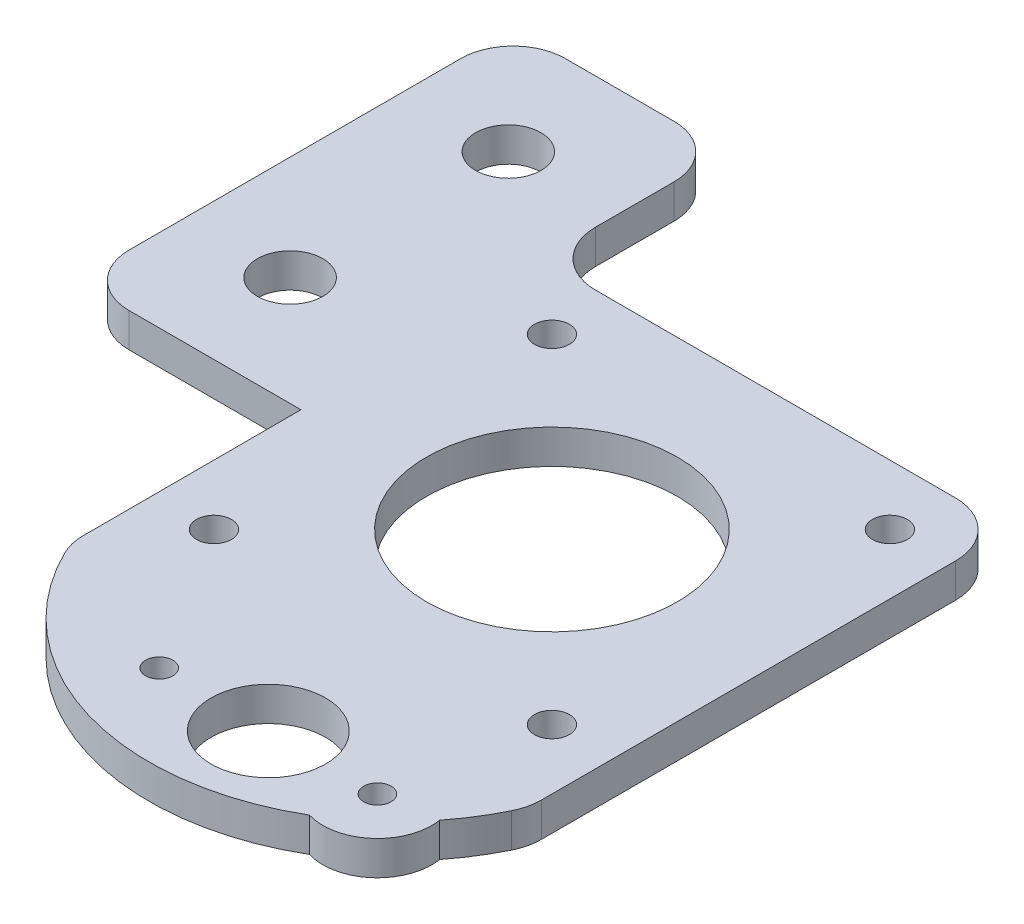
SolidWorks part; units mm, degrees
note: '?' marks a value the reader was unsure of.
ref_plane "Front Plane" through (0, 0, 0) normal (0, 0, 1) x (1, 0, 0)
ref_plane "Top Plane" through (0, 0, 0) normal (0, 1, 0) x (1, 0, 0)
ref_plane "Right Plane" through (0, 0, 0) normal (1, 0, 0) x (0, 0, -1)
ref_plane "Plane1" through (0, 546.875, 0) normal (0, -1, 0) x (1, 0, 0)
sketch "Sketch11" plane through (0, 546.875, 0) normal (0, -1, 0) x (1, 0, 0)
  line L0 (22.4103, -39.5068) -> (32.3733, -39.5068)
  line L1 (37.1733, -34.7068) -> (37.1733, -27.5068)
  line L2 (42.1733, -22.5068) -> (75.1733, -22.5068)
  line L3 (80.1733, -17.5068) -> (80.1733, 20.4615)
  line L4 (38.1828, 20.4638) -> (38.1662, 0.4932)
  line L5 (38.1662, 0.4932) -> (22.4103, 0.4932)
  line L6 (17.6103, -4.3068) -> (17.6103, -34.7068)
  arc A0 (17.6103, -34.7068) -> (22.4103, -39.5068) centre (22.4103, -34.7068) ccw
  arc A1 (32.3733, -39.5068) -> (37.1733, -34.7068) centre (32.3733, -34.7068) ccw
  arc A2 (37.1733, -27.5068) -> (42.1733, -22.5068) centre (42.1733, -27.5068) cw
  arc A3 (75.1733, -22.5068) -> (80.1733, -17.5068) centre (75.1733, -17.5068) ccw
  arc A4 (80.1733, 20.4615) -> (79.661, 22.666) centre (75.1733, 20.4615) ccw
  arc A5 (79.661, 22.666) -> (77.1125, 26.7162) centre (59.1785, 12.6046) ccw
  arc A6 (77.1125, 26.7162) -> (70.7355, 32.2821) centre (72.1733, 27.4932) ccw
  arc A7 (70.7355, 32.2821) -> (38.6947, 22.6637) centre (59.1785, 12.6046) ccw
  arc A8 (38.6947, 22.6637) -> (38.1828, 20.4638) centre (43.1828, 20.4597) ccw
  arc A9 (22.4103, 0.4932) -> (17.6103, -4.3068) centre (22.4103, -4.3068) ccw
base flange "Base-Flange1" sketch "Sketch11" thickness 3.125 reverse thickness direction yes parameters "D1"=0
hole_wizard "Ø10.5 (10.5) Diameter Hole1" positions "Sketch17" profile "Sketch16" hole size "Ø10.5" standard "ANSI Metric"
sketch "Sketch17" plane through (0, 546.875, 0) normal (0, -1, 0) x (-1, 0, 0)
  point P0 (-62.1733, -27.4932)
sketch "Sketch16" plane through (62.1733, 546.875, 27.4932) normal (1, 0, 0) x (0, 0, -1)
  line L0 (0, 0) -> (0, 3.125)
  line L1 (0, 3.125) -> (5.25, 3.125)
  line L2 (5.25, 3.125) -> (5.25, 0)
  line L5 (5.25, 0) -> (0, 0)
  line L11 (0, -6.35) -> (0, 107.95) construction
  dimension "Thru Hole Dia." = 10.5
  dimension "Thru Hole Depth" = 3.125
hole_wizard "Ø3.2 (3.2) Diameter Hole1" positions "Sketch19" profile "Sketch18" hole size "Ø3.2" standard "ANSI Metric"
sketch "Sketch19" plane through (0, 546.875, 0) normal (0, -1, 0) x (-1, 0, 0)
  point P0 (-74.6642, -13.9842)
  point P1 (-43.6823, -13.9842)
  point P2 (-43.6823, 16.9977)
  point P3 (-74.6642, 16.9977)
sketch "Sketch18" plane through (74.6642, 546.875, 13.9842) normal (1, 0, 0) x (0, 0, -1)
  line L0 (0, 0) -> (0, 3.125)
  line L1 (0, 3.125) -> (1.6, 3.125)
  line L2 (1.6, 3.125) -> (1.6, 0)
  line L5 (1.6, 0) -> (0, 0)
  line L11 (0, -6.35) -> (0, 107.95) construction
  dimension "Thru Hole Dia." = 3.2
  dimension "Thru Hole Depth" = 3.125
hole_wizard "Ø23.0 (23) Diameter Hole1" positions "Sketch21" profile "Sketch20" hole size "Ø23.0" standard "ANSI Metric"
sketch "Sketch21" plane through (0, 546.875, 0) normal (0, -1, 0) x (-1, 0, 0)
  point P0 (-59.1733, 1.5068)
sketch "Sketch20" plane through (59.1733, 546.875, -1.5068) normal (1, 0, 0) x (0, 0, -1)
  line L0 (0, 0) -> (0, 3.125)
  line L1 (0, 3.125) -> (11.5, 3.125)
  line L2 (11.5, 3.125) -> (11.5, 0)
  line L5 (11.5, 0) -> (0, 0)
  line L11 (0, -6.35) -> (0, 107.95) construction
  dimension "Thru Hole Dia." = 23
  dimension "Thru Hole Depth" = 3.125
hole_wizard "Ø6.0 (6) Diameter Hole1" positions "Sketch23" profile "Sketch22" hole size "Ø6.0" standard "ANSI Metric"
sketch "Sketch23" plane through (0, 546.875, 0) normal (0, -1, 0) x (-1, 0, 0)
  point P0 (-27.1733, 9.5068)
  point P1 (-27.1733, 29.5068)
sketch "Sketch22" plane through (27.1733, 546.875, -9.5068) normal (1, 0, 0) x (0, 0, -1)
  line L0 (0, 0) -> (0, 3.125)
  line L1 (0, 3.125) -> (3, 3.125)
  line L2 (3, 3.125) -> (3, 0)
  line L5 (3, 0) -> (0, 0)
  line L11 (0, -6.35) -> (0, 107.95) construction
  dimension "Thru Hole Dia." = 6
  dimension "Thru Hole Depth" = 3.125
hole_wizard "Ø2.5 (2.5) Diameter Hole1" positions "Sketch25" profile "Sketch24" hole size "Ø2.5" standard "ANSI Metric"
sketch "Sketch25" plane through (0, 546.875, 0) normal (0, -1, 0) x (-1, 0, 0)
  point P0 (-72.1733, -27.4932)
  point P1 (-52.1733, -27.4932)
sketch "Sketch24" plane through (72.1733, 546.875, 27.4932) normal (1, 0, 0) x (0, 0, -1)
  line L0 (0, 0) -> (0, 3.125)
  line L1 (0, 3.125) -> (1.25, 3.125)
  line L2 (1.25, 3.125) -> (1.25, 0)
  line L5 (1.25, 0) -> (0, 0)
  line L11 (0, -6.35) -> (0, 107.95) construction
  dimension "Thru Hole Dia." = 2.5
  dimension "Thru Hole Depth" = 3.125
ref_point "Point1"
ref_axis "Axis1" through (27.1733, 550, -29.5068) along (0, -1, 0)?
ref_axis "Axis2" through (27.1733, 550, -9.5068) along (0, -1, 0)?
ref_axis "Axis3" through (62.1733, 550, 27.4932) along (0, -1, 0)?
ref_axis "Axis4" through (59.1733, 550, -1.5068) along (0, -1, 0)?
sketch "Bend-Lines4" plane through (0, 0, 0) normal (0, 1, 0) x (1, 0, 0)
sketch "Bounding-Box4" plane through (0, 0, 0) normal (0, 1, 0) x (1, 0, 0)
sheet metal parameters "Sheet-Metal(6)" thickness 3.125 parameters "D1"=0
flat pattern "Flat-Pattern(6)" [suppressed]
sketch "Bend-Lines5" plane through (0, 0, 0) normal (0, 1, 0) x (1, 0, 0)
sketch "Bounding-Box5" [suppressed] plane through (0, 0, 0) normal (0, 1, 0) x (1, 0, 0)
sheet metal parameters "Sheet-Metal(7)" thickness 3.125 parameters "D1"=0
flat pattern "Flat-Pattern(6)"
sketch "Bend-Lines5" plane through (0, 0, 0) normal (0, 1, 0) x (1, 0, 0)
sketch "Bounding-Box5" [suppressed] plane through (0, 0, 0) normal (0, 1, 0) x (1, 0, 0)
sheet metal parameters "Sheet-Metal(8)" thickness 3.125 parameters "D1"=0
flat pattern "Flat-Pattern(6)"
sketch "Bend-Lines5" plane through (0, 0, 0) normal (0, 1, 0) x (1, 0, 0)
sketch "Bounding-Box5" [suppressed] plane through (0, 0, 0) normal (0, 1, 0) x (1, 0, 0)
sheet metal parameters "Sheet-Metal(9)" thickness 3.125 parameters "D1"=0
flat pattern "Flat-Pattern(6)"
sketch "Bend-Lines5" plane through (0, 0, 0) normal (0, 1, 0) x (1, 0, 0)
sketch "Bounding-Box5" [suppressed] plane through (0, 0, 0) normal (0, 1, 0) x (1, 0, 0)
sheet metal parameters "Sheet-Metal(10)" thickness 3.125 parameters "D1"=0
flat pattern "Flat-Pattern(6)"
sketch "Bend-Lines5" plane through (0, 0, 0) normal (0, 1, 0) x (1, 0, 0)
sketch "Bounding-Box5" [suppressed] plane through (0, 0, 0) normal (0, 1, 0) x (1, 0, 0)
sheet metal parameters "Sheet-Metal(11)" thickness 3.125 parameters "D1"=0
flat pattern "Flat-Pattern(6)"
sketch "Bend-Lines5" plane through (0, 0, 0) normal (0, 1, 0) x (1, 0, 0)
sketch "Bounding-Box5" [suppressed] plane through (0, 0, 0) normal (0, 1, 0) x (1, 0, 0)
